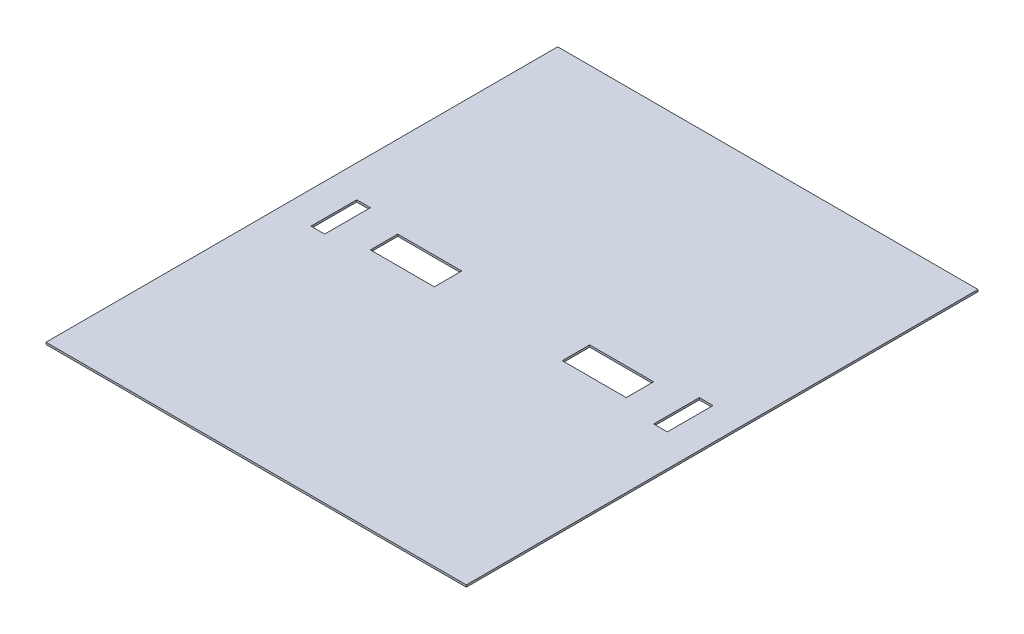
SolidWorks part; units mm, degrees
material "Plain Carbon Steel"
ref_plane "Front Plane" through (0, 0, 0) normal (0, 0, 1) x (1, 0, 0)
ref_plane "Top Plane" through (0, 0, 0) normal (0, 1, 0) x (1, 0, 0)
ref_plane "Right Plane" through (0, 0, 0) normal (1, 0, 0) x (0, 0, -1)
ref_plane "Plane1" through (0, -25.4, 330.2) normal (0, 1, 0) x (1, 0, 0)
sketch "Sketch1" plane through (0, -25.4, 330.2) normal (0, 1, 0) x (1, 0, 0)
  line L1 (292.1, 685.8) -> (-292.1, 685.8)
  line L2 (292.1, 685.8) -> (292.1, -25.4)
  line L3 (292.1, -25.4) -> (-292.1, -25.4)
  line L4 (-292.1, 685.8) -> (-292.1, -25.4)
  line L5 (292.1, 685.8) -> (-292.1, -25.4) construction
  line L6 (292.1, -25.4) -> (-292.1, 685.8) construction
  point P0 (0, 330.2)
extrude "Boss-Extrude1" add sketch "Sketch1" against normal blind 2.794
sketch "Sketch3" plane through (0, -28.194, 0) normal (0, -1, 0) x (-1, 0, 0)
  line L0 (228.6, 0) -> (177.8, 0) construction
  line L1 (247.65, -31.75) -> (228.6, -31.75)
  line L2 (247.65, -31.75) -> (247.65, 31.75)
  line L3 (247.65, 31.75) -> (228.6, 31.75)
  line L4 (228.6, -31.75) -> (228.6, 31.75)
  line L5 (292.1, 355.6) -> (292.1, -355.6) construction
  line L6 (177.8, -19.05) -> (88.9, -19.05)
  line L7 (177.8, -19.05) -> (177.8, 19.05)
  line L8 (177.8, 19.05) -> (88.9, 19.05)
  line L9 (88.9, -19.05) -> (88.9, 19.05)
  point P10 (0, 0)
  dimension "D1" = 38.1
  dimension "D2" = 63.5
  dimension "D3" = 19.05
  dimension "D4" = 88.9
  dimension "D5" = 44.45
  dimension "D6" = 50.8
extrude "Cut-Extrude1" cut sketch "Sketch3" against normal through all
mirror "Mirror1" about plane through (0, 0, 0) normal (1, 0, 0) of "Cut-Extrude1"
